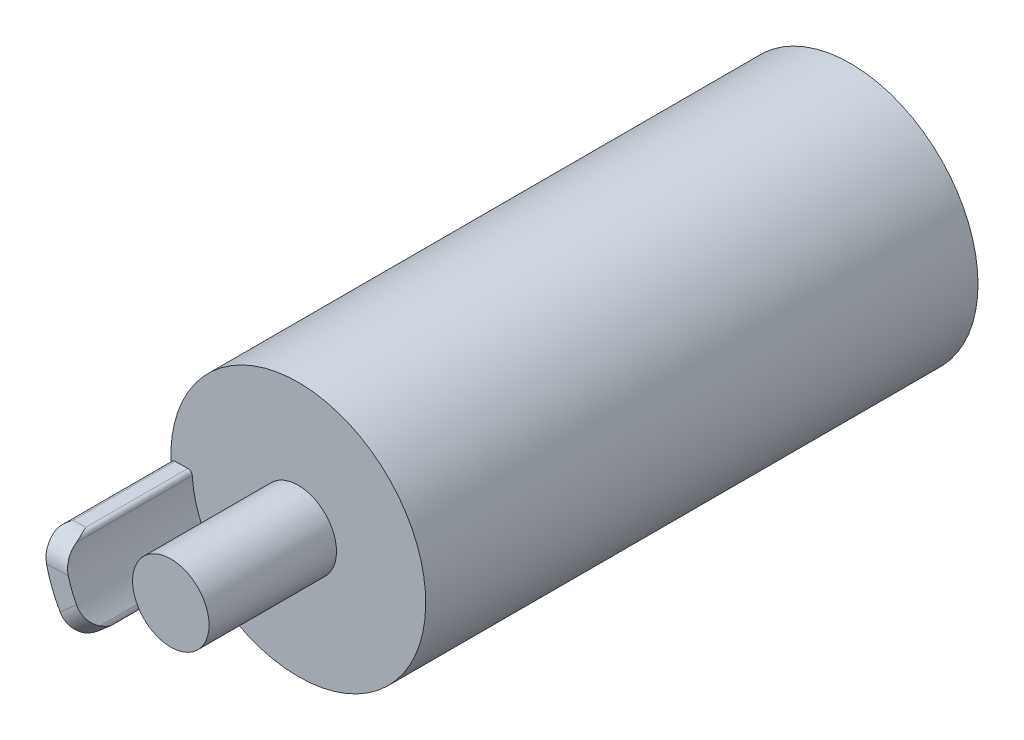
SolidWorks part; units mm, degrees
ref_plane "前视基准面" through (0, 0, 0) normal (0, 0, 1) x (1, 0, 0)
ref_plane "上视基准面" through (0, 0, 0) normal (0, 1, 0) x (1, 0, 0)
ref_plane "右视基准面" through (0, 0, 0) normal (1, 0, 0) x (0, 0, -1)
sketch "草图1" plane through (0, 0, 0) normal (0, 0, 1) x (1, 0, 0)
  circle A0 centre (0, 0) radius 3
  circle A1 centre (0, 0) radius 1.8
  dimension "D1" = 6
  dimension "D2" = 3.6
extrude "凸台-拉伸1" add sketch "草图1" along normal blind 13
sketch "草图2" plane through (0, 0, 13) normal (0, 0, 1) x (1, 0, 0)
  circle A0 centre (0, 0) radius 0.9
  dimension "D1" = 1.8
extrude "凸台-拉伸2" add sketch "草图2" against normal blind 11 and the other way blind 3 separate body
fillet "圆角1" radius 0.5 1 edges at (0.9, 0, 2)
sketch "草图3" plane through (0, 0, 13) normal (0, 0, 1) x (1, 0, 0)
  circle A1 centre (0, 0) radius 3
  circle A2 centre (0, 0) radius 3
  dimension "D1" = 0
extrude "凸台-拉伸3" add sketch "草图3" against normal blind 1
sketch "草图4" plane through (0, 0, 13) normal (0, 0, 1) x (1, 0, 0)
  line L0 (-2.5975, -0.0552) -> (-2.8976, -0.0616)
  line L1 (-1.9543, -1.7119) -> (-2.1801, -1.9097)
  arc A0 (-2.9953, -0.1671) -> (-2.3235, -1.8978) centre (0, 0) ccw
  arc A1 (-2.4955, -0.1492) -> (-1.9425, -1.5737) centre (0, 0) ccw
  circle A2 centre (0, 0) radius 3 construction
  arc A3 (-2.1801, -1.9097) -> (-2.3235, -1.8978) centre (-2.246, -1.8345) cw
  arc A4 (-2.8976, -0.0616) -> (-2.9953, -0.1671) centre (-2.8955, -0.1615) ccw
  arc A5 (-1.9425, -1.5737) -> (-1.9543, -1.7119) centre (-2.0202, -1.6367) cw
  arc A6 (-2.4955, -0.1492) -> (-2.5975, -0.0552) centre (-2.5954, -0.1552) ccw
  dimension "D1" = 0.5
  dimension "D2" = 0
  dimension "D4" = 0.1
  dimension "D3" = 40
extrude "凸台-拉伸4" add sketch "草图4" along normal blind 3
fillet "圆角2" radius 0.6 2 edges at (-2.7476, -0.0584, 16) (-2.0672, -1.8108, 16) tangent propagation no
